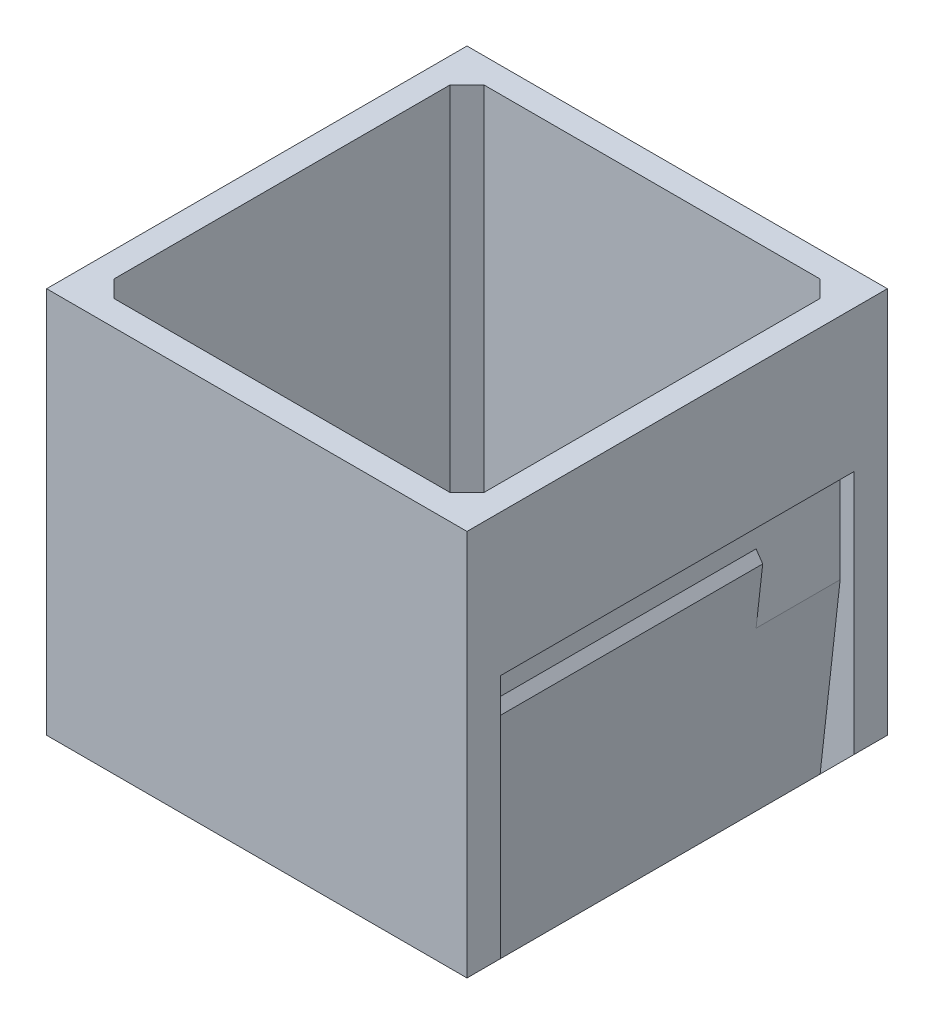
SolidWorks part; units mm, degrees
ref_plane "Ebene vorne" through (0, 0, 0) normal (0, 0, 1) x (1, 0, 0)
ref_plane "Ebene oben" through (0, 0, 0) normal (0, 1, 0) x (1, 0, 0)
ref_plane "Ebene rechts" through (0, 0, 0) normal (1, 0, 0) x (0, 0, -1)
sketch "Skizze1" plane through (0, 0, 0) normal (0, 1, 0) x (1, 0, 0)
  line L1 (-12.5, -12.5) -> (12.5, -12.5)
  line L2 (-12.5, -12.5) -> (-12.5, 12.5)
  line L3 (-12.5, 12.5) -> (12.5, 12.5)
  line L4 (12.5, -12.5) -> (12.5, 12.5)
  line L5 (-12.5, -12.5) -> (12.5, 12.5) construction
  line L6 (-12.5, 12.5) -> (12.5, -12.5) construction
  point P0 (0, 0)
  dimension "D1" = 25
  dimension "D2" = 25
extrude "Aufsatz-Linear austragen1" add sketch "Skizze1" along normal blind 25
chamfer "Fase1" distance 2 angle 45 4 edges at (0, 0, -12.5) (-12.5, 0, 0) (0, 0, 12.5) (12.5, 0, 0)
sketch "Skizze3" plane through (0, 0, 12.5) normal (0, 0, 1) x (1, 0, 0)
  line L0 (11.6914, 15.7981) -> (11.6914, 14.6981)
  line L2 (12.5, 16.5764) -> (12.5, 0)
  line L3 (12.5, 0) -> (10.5, 0)
  line L5 (12.5, 16.5764) -> (11.6914, 15.7981)
  line L6 (11.6914, 14.6981) -> (12.0854, 14.1191)
  line L7 (12.0854, 14.1191) -> (10.5, 0)
  line L8 (10.5, 0) -> (12.5, 0)
  line L9 (12.5, 25) -> (12.5, 2) construction
  line M2 (-12.5, 2) -> (12.5, 2)
  line M3 (12.5, 2) -> (12.5, 25)
  dimension "D1" = 1.1
extrude "Schnitt-Linear austragen1" cut sketch "Skizze3" against normal blind 21 from offset 2 contours L6 L7 L5 M2 M3 | L7 L3 L2 M2 region at (11.9094, 7.6896, 12.5) region at (11.555, 0.9802, 12.5) offset against normal yes
shell "Wandung1" thickness 1.5 removed face at (0, 25, 0)
chamfer "Fase2" distance 1 angle 45 4 edges at (11, 21.1073, 11) (-11, 13.8107, 11) (-11, 13.8107, -11) (11, 21.1073, -11)
sketch "Skizze4" plane through (0, 0, -10.5) normal (0, 0, 1) x (1, 0, 0)
  line L0 (11.6914, 15.7981) -> (11.6914, 11.7202)
  line L1 (11.6914, 11.7202) -> (11.6914, 10.6102)
  line L2 (12.0854, 14.1191) -> (10.5, 0) construction
  line L3 (11.6914, 10.6102) -> (10.5, 0)
  line L4 (10.5, 0) -> (12.5, 2)
  line L5 (12.5, 2) -> (12.5, 16.5764)
  line L6 (12.5, 2) -> (12.5, 16.5764) construction
  line L7 (12.5, 16.5764) -> (11.6914, 15.7981) construction
  line L8 (12.5, 16.5764) -> (11.6914, 15.7981)
extrude "Schnitt-Linear austragen2" cut sketch "Skizze4" along normal blind 5
